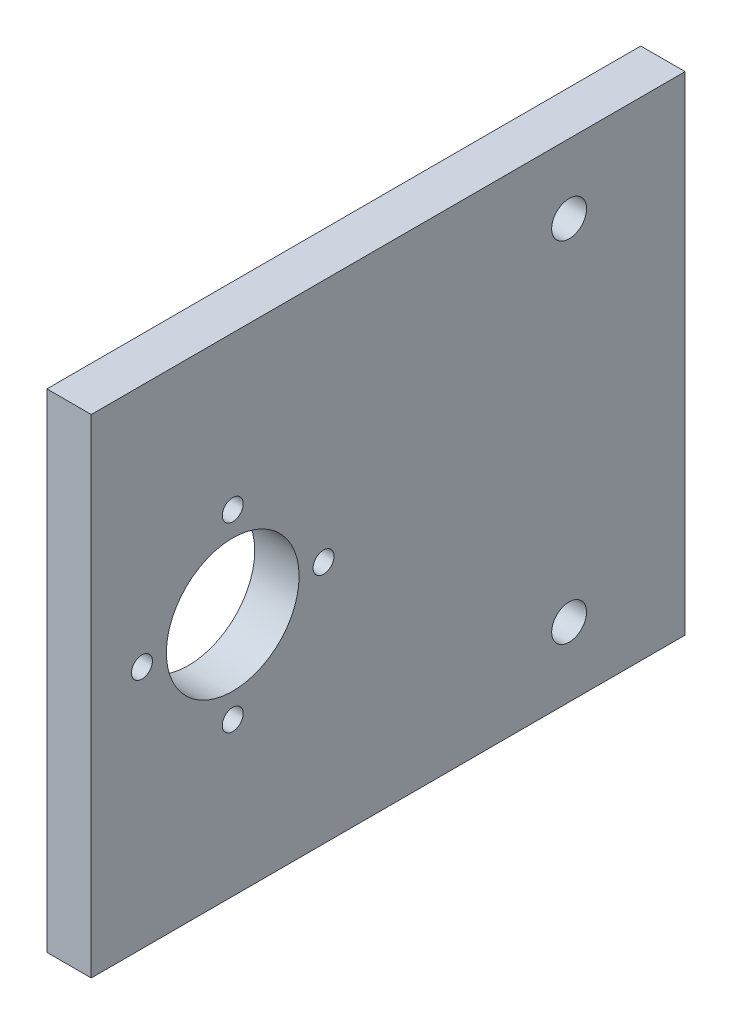
SolidWorks part; units mm, degrees
ref_plane "Front Plane" through (0, 0, 0) normal (1, 0, 0) x (0, 1, 0)
ref_plane "Top Plane" through (0, 0, 0) normal (0, 0, 1) x (0, 1, 0)
ref_plane "Right Plane" through (0, 0, 0) normal (0, 1, 0) x (-1, 0, 0)
sketch "Sketch1" plane through (0, 0, 0) normal (1, 0, 0) x (0, 1, 0)
  line L0 (0, 42.5) -> (0, -42.5) construction
  line L1 (-34.925, -42.5) -> (34.925, -42.5)
  line L2 (-34.925, -42.5) -> (-34.925, 42.5)
  line L3 (-34.925, 42.5) -> (34.925, 42.5)
  line L4 (34.925, -42.5) -> (34.925, 42.5)
  line L5 (-34.925, -42.5) -> (34.925, 42.5) construction
  line L6 (-34.925, 42.5) -> (34.925, -42.5) construction
  line L7 (-34.925, 22.25) -> (34.925, 22.25) construction
  line L9 (-25, -25.9) -> (25, -25.9) construction
  line L10 (-25, -25.9) -> (-25, 25.9) construction
  line L11 (-25, 25.9) -> (25, 25.9) construction
  line L12 (25, -25.9) -> (25, 25.9) construction
  line L13 (-25, -25.9) -> (25, 25.9) construction
  line L14 (-25, 25.9) -> (25, -25.9) construction
  circle A1 centre (0, 35.25) radius 1.5
  circle A2 centre (0, 9.25) radius 1.5
  circle A3 centre (-13, 22.25) radius 1.5
  circle A4 centre (13, 22.25) radius 1.5
  circle A5 centre (0, 22.25) radius 9.5
  circle A6 centre (-25, -25.9) radius 2.5
  circle A7 centre (25, -25.9) radius 2.5
  point P0 (0, 0)
  point P20 (0, 0)
  dimension "D5" = 3
  dimension "D6" = 3
  dimension "D7" = 13
  dimension "D8" = 19
  dimension "D11" = 5
  dimension "D12" = 5
  dimension "D1" = 69.85
  dimension "D2" = 85
  dimension "D3" = 64.75
  dimension "D4" = 13
  dimension "D9" = 16.6
  dimension "D10" = 50
extrude "Boss-Extrude1" add sketch "Sketch1" along normal blind 6.35
